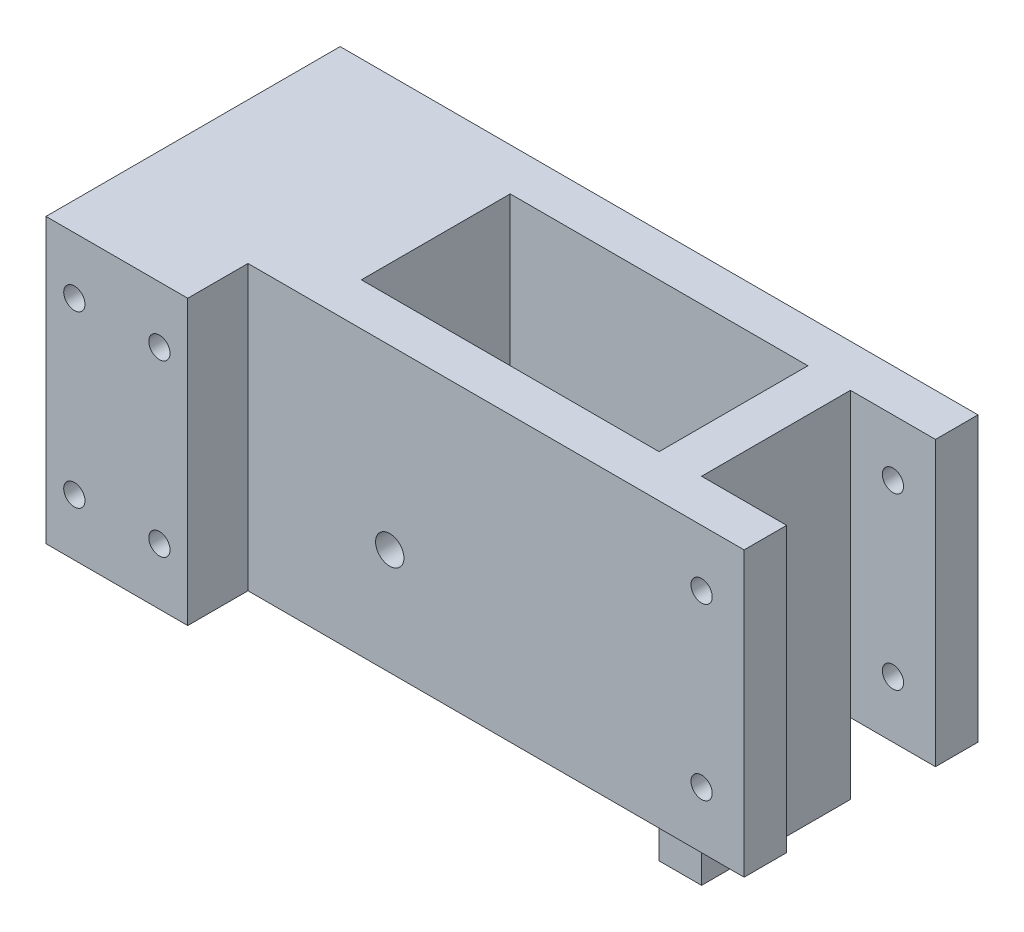
SolidWorks part; units mm, degrees
ref_plane "前视基准面" through (0, 0, 0) normal (0, 0, 1) x (1, 0, 0)
ref_plane "上视基准面" through (0, 0, 0) normal (0, 1, 0) x (1, 0, 0)
ref_plane "右视基准面" through (0, 0, 0) normal (1, 0, 0) x (0, 0, -1)
other "Configuration Table"
sketch "草图1" plane through (0, 0, 0) normal (0, 1, 0) x (1, 0, 0)
  line L1 (0, 0) -> (90, 0)
  line L3 (0, 33) -> (90, 33)
  line L9 (0, 33) -> (0, 0)
  line L10 (90, 33) -> (90, 27)
  line L11 (90, 27) -> (30, 27)
  line L12 (30, 27) -> (30, 6)
  line L13 (30, 6) -> (90, 6)
  line L14 (90, 6) -> (90, 0)
  dimension "D1" = 21
  dimension "D2" = 60
  dimension "D3" = 6
  dimension "D4" = 6
  dimension "D5" = 90
extrude "凸台-拉伸1" add sketch "草图1" along normal blind 40
sketch "草图7" plane through (0, 40, 0) normal (0, 1, 0) x (1, 0, 0)
  line L1 (20, -8.5) -> (0, -8.5)
  line L2 (20, -8.5) -> (20, 0)
  line L3 (20, 0) -> (0, 0)
  line L4 (0, -8.5) -> (0, 0)
  line L6 (0, 0) -> (90, 0) construction
  line L7 (0, 33) -> (0, 0) construction
  dimension "D1" = 8.5
  dimension "D2" = 20
extrude "凸台-拉伸5" add sketch "草图7" against normal up to surface (40 mm away) up to face at (52.5, 0, -16.5)
sketch "草图8" plane through (0, 0, -33) normal (0, 0, -1) x (-1, 0, 0)
  line L0 (-90, 40) -> (-90, 0) construction
  line L1 (-84, 32) -> (-16, 32) construction
  line L2 (-84, 32) -> (-84, 8) construction
  line L3 (-84, 8) -> (-16, 8) construction
  line L4 (-16, 32) -> (-16, 8) construction
  line L5 (-90, 40) -> (0, 40) construction
  circle A0 centre (-84, 8) radius 1.5
  circle A1 centre (-84, 32) radius 1.5
  circle A2 centre (-16, 32) radius 1.5
  circle A3 centre (-16, 8) radius 1.5
  dimension "D4" = 3
  dimension "D1" = 68
  dimension "D2" = 24
  dimension "D3" = 6
  dimension "D5" = 8
extrude "切除-拉伸2" cut sketch "草图8" against normal through all
sketch "草图9" plane through (0, 0, 8.5) normal (0, 0, 1) x (1, 0, 0)
  line L0 (4, 32) -> (16, 32) construction
  line L1 (4, 8) -> (16, 8) construction
  circle A0 centre (4, 32) radius 1.5
  circle A1 centre (4, 8) radius 1.5
  circle A3 centre (16, 32) radius 1.5 construction
  circle A4 centre (16, 8) radius 1.5 construction
  dimension "D1" = 3
  dimension "D2" = 3
  dimension "D3" = 12
extrude "切除-拉伸3" cut sketch "草图9" against normal through all
sketch "草图10" plane through (0, 40, 0) normal (0, 1, 0) x (1, 0, 0)
  line L0 (30, 27) -> (90, 27) construction
  line L1 (78, 27) -> (72, 27)
  line L2 (78, 27) -> (78, 6)
  line L3 (78, 6) -> (72, 6)
  line L4 (72, 27) -> (72, 6)
  line L5 (90, 6) -> (30, 6) construction
  line L7 (30, 6) -> (30, 27) construction
  dimension "D1" = 42
  dimension "D2" = 6
extrude "凸台-拉伸6" add sketch "草图10" along direction (0, 1, 0) on the side against the normal blind 10 and the other way up to surface from surface other way up to face at (46, 40, -11.5) starting at face at (46, 0, -11.5)
sketch "草图11" plane through (0, 0, 0) normal (0, 0, 1) x (1, 0, 0)
  line L0 (20, 0) -> (90, 0) construction
  line L1 (20, 0) -> (20, 40) construction
  circle A0 centre (40, 15) radius 2
  dimension "D2" = 4
  dimension "D1" = 15
  dimension "D3" = 20
extrude "切除-拉伸4" cut sketch "草图11" against normal through all
